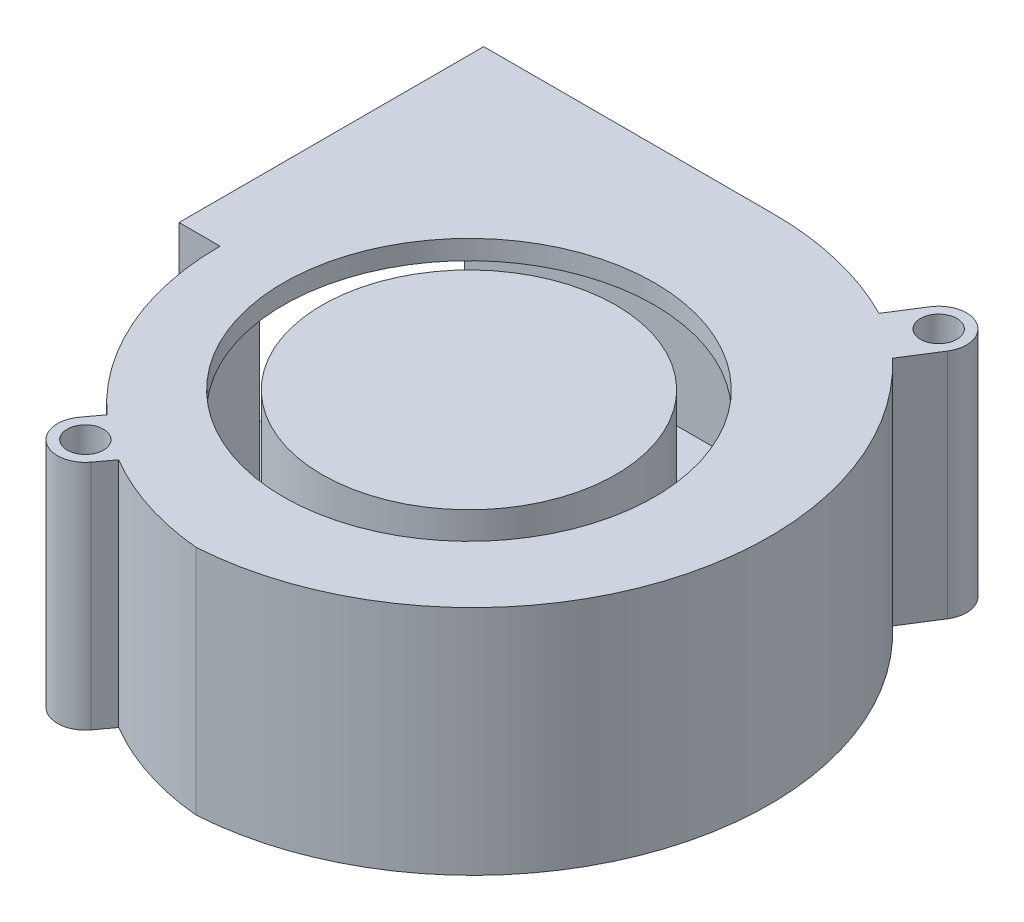
SolidWorks part; units mm, degrees
ref_plane "Front Plane" through (0, 0, 0) normal (0, 0, 1) x (1, 0, 0)
ref_plane "Top Plane" through (0, 0, 0) normal (0, 1, 0) x (1, 0, 0)
ref_plane "Right Plane" through (0, 0, 0) normal (1, 0, 0) x (0, 0, -1)
sketch "Sketch1" plane through (0, 0, 0) normal (0, 1, 0) x (1, 0, 0)
  line L0 (-36.7, 37.35) -> (-36.7, -2.06)
  line L1 (-36.7, -37.35) -> (36.7, -37.35) construction
  line L2 (-36.7, -37.35) -> (-36.7, 37.35) construction
  line L3 (-36.7, 37.35) -> (36.7, 37.35) construction
  line L4 (36.7, -37.35) -> (36.7, 37.35) construction
  line L5 (-36.7, -37.35) -> (36.7, 37.35) construction
  line L6 (-36.7, 37.35) -> (36.7, -37.35) construction
  line L7 (-36.7, -2.06) -> (-31.4, -2.06)
  line L8 (-36.7, 37.35) -> (0.8, 37.35)
  line L9 (-31.4, -2.06) -> (-31.4, -37.35) construction
  line L10 (-36.7, -2.06) -> (36.7, -2.06) construction
  line L11 (0.8, 37.35) -> (0.8, -37.35) construction
  line L12 (-78.9719, 116.2867) -> (254.3615, 116.2867) construction
  line L13 (27.3919, 33.2225) -> (24.6405, 28.8754)
  line L14 (21.3081, 37.0731) -> (18.7485, 33.0291)
  line L15 (-21.3293, -30.3095) -> (-19.8181, -28.2658)
  line L16 (-15.5403, -34.5905) -> (-14.029, -32.5468)
  line L17 (24.35, 35.1478) -> (-18.4348, -32.45) construction
  arc A0 (0.8, 37.35) -> (18.7485, 33.0291) centre (0.8, -2.0882) cw
  arc A1 (-31.4, -2.06) -> (-19.8181, -28.2658) centre (4.0383, -2.06) ccw
  circle A2 centre (0.8, -2.06) radius 24 construction
  arc A3 (27.3919, 33.2225) -> (21.3081, 37.0731) centre (24.35, 35.1478) ccw
  arc A4 (-21.3293, -30.3095) -> (-15.5403, -34.5905) centre (-18.4348, -32.45) ccw
  arc A5 (24.6405, 28.8754) -> (0.8, -37.35) centre (-1.6745, 0.9447) cw
  arc A6 (-14.029, -32.5468) -> (0.8, -37.35) centre (4.0383, -2.06) ccw
  arc A7 (18.7485, 33.0291) -> (24.6405, 28.8754) centre (7.1222, 10.2815) cw construction
  point P0 (0, 0)
  point P19 (19.5942, 34.3652)
  point P23 (24.6405, 28.8754)
  dimension "D5" = 48
  dimension "D10" = 7.2
  dimension "D1" = 73.4
  dimension "D2" = 74.7
  dimension "D3" = 39.41
  dimension "D4" = 37.5
  dimension "D6" = 5.3
  dimension "D7" = 23.55
  dimension "D8" = 80
  dimension "D9" = 7.2
  dimension "D11" = 69.8
extrude "Boss-Extrude1" add sketch "Sketch1" along normal blind 30 contours L16 A6 A5 L8 L0 L7 A1 L15 A4 region at (-0.7394, 0, -2.9255)
shell "Shell1" thickness 2.5 removed face at (-36.7, 15, -17.645)
sketch "Sketch2" plane through (0, 30, 0) normal (0, 1, 0) x (1, 0, 0)
  circle A0 centre (0.8, -2.06) radius 24 construction
  circle A1 centre (0.8, -2.06) radius 24
extrude "Cut-Extrude1" cut sketch "Sketch2" against normal blind 14
sketch "Sketch3" plane through (0, 2.5, 0) normal (0, 1, 0) x (1, 0, 0)
  circle A1 centre (0.8, -2.06) radius 19
  dimension "D1" = 38
extrude "Boss-Extrude2" add sketch "Sketch3" along normal up to surface (27.5 mm away) up to face at (0.8, 30, 26.06)
sketch "Sketch4" plane through (0, 30, 0) normal (0, 1, 0) x (1, 0, 0)
  circle A0 centre (24.35, 35.1478) radius 2.35
  circle A1 centre (-18.4348, -32.45) radius 2.35
  arc A2 (27.3919, 33.2225) -> (21.3081, 37.0731) centre (24.35, 35.1478) ccw construction
  point P6 (0, 0)
  point P7 (23.362, 32.7432)
  dimension "D1" = 4.7
extrude "Cut-Extrude2" cut sketch "Sketch4" against normal through all
